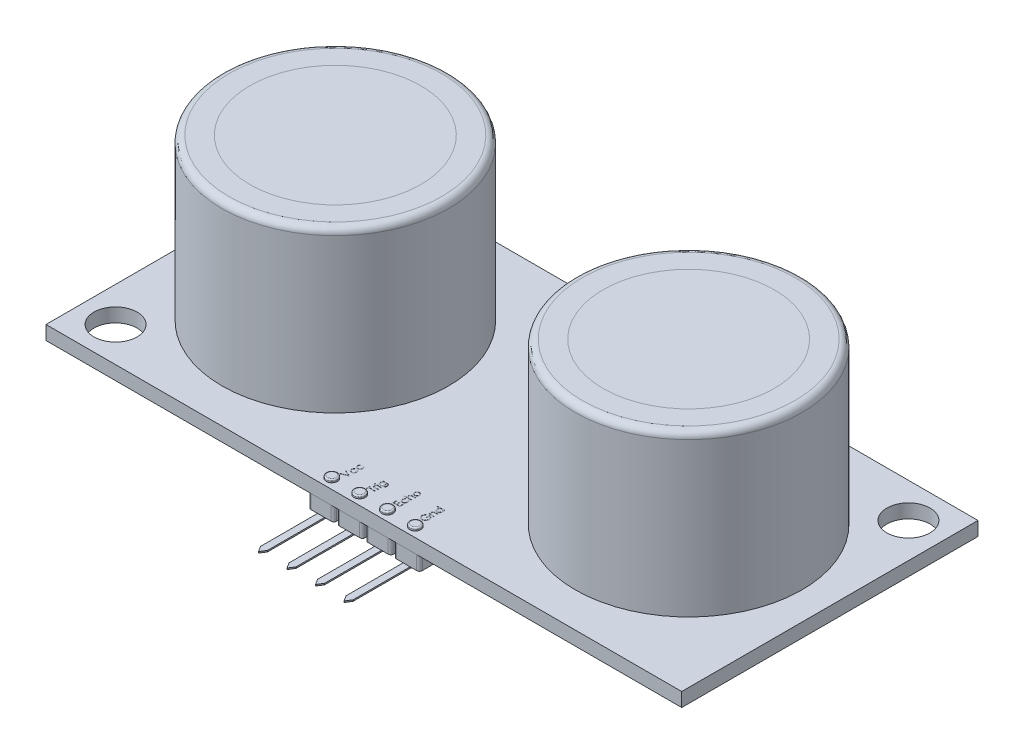
SolidWorks part; units mm, degrees
ref_plane "Front Plane" through (0, 0, 0) normal (0, 0, 1) x (1, 0, 0)
ref_plane "Top Plane" through (0, 0, 0) normal (0, 1, 0) x (1, 0, 0)
ref_plane "Right Plane" through (0, 0, 0) normal (1, 0, 0) x (0, 0, -1)
sketch "Sketch1" plane through (0, 0, 0) normal (0, 1, 0) x (1, 0, 0)
  line L1 (22.85, -10.65) -> (-22.85, -10.65)
  line L2 (22.85, -10.65) -> (22.85, 10.65)
  line L3 (22.85, 10.65) -> (-22.85, 10.65)
  line L4 (-22.85, -10.65) -> (-22.85, 10.65)
  line L5 (22.85, -10.65) -> (-22.85, 10.65) construction
  line L6 (22.85, 10.65) -> (-22.85, -10.65) construction
  circle A0 centre (20.35, 8.15) radius 1.55
  circle A1 centre (-20.35, -8.15) radius 1.55
  point P0 (0, 0)
  dimension "D3" = 3.1
  dimension "D1" = 45.7
  dimension "D2" = 21.3
  dimension "D4" = 2.5
  dimension "D5" = 2.5
  dimension "D6" = 2.5
  dimension "D7" = 2.5
extrude "Boss-Extrude1" add sketch "Sketch1" along normal blind 1
sketch "Sketch2" plane through (0, 1, 0) normal (0, 1, 0) x (1, 0, 0)
  line L0 (0, 0) -> (0, -50000) construction
  circle A0 centre (-12.7, 0) radius 8.15
  circle A1 centre (12.7, 0) radius 8.15
  circle A2 centre (-12.7, 0) radius 6.15
  circle A3 centre (12.7, 0) radius 6.15
  point P4 (20.85, 0)
  point P6 (-20.85, 0)
  dimension "D1" = 16.3
  dimension "D2" = 41.7
  dimension "D3" = 20.85
  dimension "D4" = 2
extrude "Boss-Extrude2" add sketch "Sketch2" along normal blind 11.54 separate body
fillet "Fillet1" radius 0.5 1 edges at (-12.7, 12.54, 8.15)
fillet "Fillet2" radius 0.5 1 edges at (12.7, 12.54, 8.15)
sketch "Sketch3" plane through (0, 1, 0) normal (0, 1, 0) x (1, 0, 0)
  circle A0 centre (-12.7, 0) radius 6
  circle A1 centre (12.7, 0) radius 6
  dimension "D1" = 12
extrude "Boss-Extrude3" add sketch "Sketch3" along normal blind 7 separate body
ref_plane "Plane1" through (12.7, 0, 0) normal (1, 0, 0) x (0, 0, -1)
sketch "Sketch5" plane through (12.7, 0, 0) normal (1, 0, 0) x (0, 0, -1)
  line L0 (0, 8) -> (0, -49992) construction
  line L1 (6, 8) -> (-6, 8) construction
  line L2 (0.75, 8.5) -> (0.75, 8.4)
  line L4 (0.75, 8.5) -> (0, 8.5)
  line L5 (4, 8.915) -> (2, 8)
  line L6 (0.75, 8.4) -> (0.95, 8.4)
  line L7 (0, 8.5) -> (0, 8)
  line L8 (0, 8) -> (2, 8)
  line L9 (0.95, 8.4) -> (4, 8.915)
  point P4 (0, 8)
  dimension "D1" = 4
  dimension "D2" = 0.5
  dimension "D3" = 0.75
  dimension "D4" = 0.1
  dimension "D5" = 2
  dimension "D6" = 15
  dimension "D7" = 0.2
revolve "Revolve1" add sketch "Sketch5" angle 360 about L0
pattern_linear "LPattern2" count 2 spacing 25.4 along (-1, 0, 0) of "Revolve1"
sketch "Sketch6" plane through (0, 12.54, 0) normal (0, 1, 0) x (1, 0, 0)
  circle A0 centre (-12.7, 0) radius 6.15
  circle A1 centre (12.7, 0) radius 6.15
  dimension "D1" = 12.3
extrude "Boss-Extrude4" add sketch "Sketch6" against normal blind 0.2 separate body
sketch "Sketch18" plane through (0, 0, 0) normal (0, -1, 0) x (1, 0, 0)
  line L0 (-22.85, 10.65) -> (22.85, 10.65) construction
  line L1 (-3.8, 10.65) -> (-2.35, 10.65)
  line L2 (-4, 10.45) -> (-4, 8.85)
  line L3 (-3.8, 8.65) -> (-2.35, 8.65)
  line L4 (4, 10.45) -> (4, 8.85)
  line L5 (0, 8.65) -> (0, 10.65) construction
  line L6 (-4, 9.65) -> (4, 9.65) construction
  line L7 (0, 0) -> (0, 50000) construction
  line L8 (-2.15, 10.45) -> (-2.15, 8.85)
  line L9 (0.1, 10.45) -> (0.1, 8.85)
  line L10 (-1.95, 10.45) -> (-1.95, 8.85)
  line L11 (-1.75, 10.65) -> (-0.3, 10.65)
  line L12 (-1.75, 8.65) -> (-0.3, 8.65)
  line L13 (-0.1, 8.85) -> (-0.1, 10.45)
  line L14 (0.3, 10.65) -> (1.75, 10.65)
  line L15 (0.3, 8.65) -> (1.75, 8.65)
  line L16 (1.95, 10.45) -> (1.95, 8.85)
  line L17 (2.15, 10.45) -> (2.15, 8.85)
  line L18 (2.35, 10.65) -> (3.8, 10.65)
  line L19 (2.35, 8.65) -> (3.8, 8.65)
  arc A0 (3.8, 8.65) -> (4, 8.85) centre (3.8, 8.85) ccw
  arc A1 (4, 10.45) -> (3.8, 10.65) centre (3.8, 10.45) ccw
  arc A2 (2.15, 8.85) -> (2.35, 8.65) centre (2.35, 8.85) ccw
  arc A3 (2.15, 10.45) -> (2.35, 10.65) centre (2.35, 10.45) cw
  arc A4 (1.95, 8.85) -> (1.75, 8.65) centre (1.75, 8.85) cw
  arc A5 (1.95, 10.45) -> (1.75, 10.65) centre (1.75, 10.45) ccw
  arc A6 (0.1, 8.85) -> (0.3, 8.65) centre (0.3, 8.85) ccw
  arc A7 (0.1, 10.45) -> (0.3, 10.65) centre (0.3, 10.45) cw
  arc A8 (-0.1, 8.85) -> (-0.3, 8.65) centre (-0.3, 8.85) cw
  arc A9 (-0.1, 10.45) -> (-0.3, 10.65) centre (-0.3, 10.45) ccw
  arc A10 (-1.95, 10.45) -> (-1.75, 10.65) centre (-1.75, 10.45) cw
  arc A11 (-1.95, 8.85) -> (-1.75, 8.65) centre (-1.75, 8.85) ccw
  arc A12 (-2.35, 8.65) -> (-2.15, 8.85) centre (-2.35, 8.85) ccw
  arc A13 (-2.15, 10.45) -> (-2.35, 10.65) centre (-2.35, 10.45) ccw
  arc A14 (-4, 8.85) -> (-3.8, 8.65) centre (-3.8, 8.85) ccw
  arc A15 (-4, 10.45) -> (-3.8, 10.65) centre (-3.8, 10.45) cw
  point P24 (4, 10.65)
  point P27 (2.15, 8.65)
  point P30 (2.15, 10.65)
  point P33 (1.95, 8.65)
  point P38 (0.1, 8.65)
  point P41 (0.1, 10.65)
  point P46 (-0.1, 10.65)
  point P49 (-1.95, 10.65)
  point P52 (-1.95, 8.65)
  point P59 (-4, 8.65)
  point P62 (-4, 10.65)
  point P212 (0, 9.65)
  dimension "D1" = 8
  dimension "D10" = 0.2
  dimension "D2" = 2
  dimension "D3" = 1.85
  dimension "D4" = 0.2
  dimension "D5" = 1.85
  dimension "D6" = 0.2
  dimension "D7" = 0.2
  dimension "D8" = 1.85
  dimension "D9" = 4
extrude "Boss-Extrude10" add sketch "Sketch18" along normal blind 1 separate body
sketch "Sketch13" plane through (0, 1, 0) normal (0, 1, 0) x (1, 0, 0)
  line L0 (-4, -10.65) -> (-4, -8.7338) construction
  line L1 (-22.85, -10.65) -> (22.85, -10.65) construction
  line L2 (-4, -8.7338) -> (4, -8.7338) construction
  line L3 (4, -8.7338) -> (4, -10.65) construction
  line L4 (4, -10.65) -> (-4, -10.65) construction
  line L5 (0, 0) -> (0, -50000) construction
  circle A0 centre (-3, -9.95) radius 0.4
  circle A1 centre (-1, -9.95) radius 0.4
  circle A2 centre (1, -9.95) radius 0.4
  circle A3 centre (3, -9.95) radius 0.4
  point P9 (-4, -9.6919)
  dimension "D8" = 0.8
  dimension "D1" = 8
  dimension "D2" = 4
  dimension "D3" = 0.7
  dimension "D4" = 2
  dimension "D5" = 2
  dimension "D6" = 2
  dimension "D7" = 1
extrude "Boss-Extrude8" add sketch "Sketch13" along normal blind 0.2 separate body
fillet "Fillet3" radius 0.1 1 edges at (-3, 1.2, 10.35)
fillet "Fillet4" radius 0.1 1 edges at (-1, 1.2, 10.35)
fillet "Fillet5" radius 0.1 1 edges at (1, 1.2, 10.35)
fillet "Fillet6" radius 0.1 1 edges at (3, 1.2, 10.35)
sketch "Sketch15" plane through (0, 1, 0) normal (0, 1, 0) x (1, 0, 0)
  line L0 (-22.85, -10.65) -> (22.85, -10.65) construction
  line L1 (3.4865, -7.65) -> (-2.4849, -7.65) construction
  line L2 (3.4865, -7.65) -> (3.4865, -10.65) construction
  line L3 (3.4865, -10.65) -> (-2.4849, -10.65) construction
  line L5 (-2.4849, -7.65) -> (-2.4849, -10.65) construction
  line L6 (3.4865, -7.65) -> (-2.4849, -10.65) construction
  line L7 (3.4865, -10.65) -> (-2.4849, -7.65) construction
  text T0 "Vcc  \r\nTrig   \r\nEcho\r\nGnd " font "Century Gothic" height 0.5
  point P0 (0.5008, -9.15)
  dimension "D1" = 3
extrude "Cut-Extrude5" cut sketch "Sketch15" against normal blind 0.01
sketch "Sketch19" plane through (0, -1, 0) normal (0, -1, 0) x (1, 0, 0)
  line L1 (3.325, 9.15) -> (2.825, 9.15)
  line L2 (3.325, 9.15) -> (3.325, 14.75)
  line L3 (3.075, 15.15) -> (2.825, 15.15)
  line L4 (2.825, 9.15) -> (2.825, 14.75)
  line L5 (3.075, 15.15) -> (3.075, 9.15) construction
  line L6 (3.325, 12.15) -> (2.825, 12.15) construction
  line L7 (1.275, 9.15) -> (0.775, 9.15)
  line L8 (1.275, 9.15) -> (1.275, 14.75)
  line L9 (1.025, 15.15) -> (0.775, 15.15)
  line L10 (0.775, 9.15) -> (0.775, 14.75)
  line L11 (1.025, 15.15) -> (1.025, 9.15) construction
  line L12 (1.275, 12.15) -> (0.775, 12.15) construction
  line L13 (-0.775, 9.15) -> (-1.275, 9.15)
  line L14 (-0.775, 9.15) -> (-0.775, 14.75)
  line L15 (-1.025, 15.15) -> (-1.275, 15.15)
  line L16 (-1.275, 9.15) -> (-1.275, 14.75)
  line L17 (-1.025, 15.15) -> (-1.025, 9.15) construction
  line L18 (-0.775, 12.15) -> (-1.275, 12.15) construction
  line L19 (-2.825, 9.15) -> (-3.325, 9.15)
  line L20 (-2.825, 9.15) -> (-2.825, 14.75)
  line L21 (-3.075, 15.15) -> (-3.325, 15.15)
  line L22 (-3.325, 9.15) -> (-3.325, 14.75)
  line L23 (-3.075, 15.15) -> (-3.075, 9.15) construction
  line L24 (-2.825, 12.15) -> (-3.325, 12.15) construction
  line L26 (-1.75, 8.65) -> (-0.3, 8.65) construction
  line L27 (-3.8, 8.65) -> (-2.35, 8.65) construction
  line L29 (-3.075, 15.15) -> (-2.825, 14.75)
  line L30 (-3.075, 15.15) -> (-3.325, 14.75)
  line L31 (-1.025, 15.15) -> (-0.775, 14.75)
  line L32 (1.025, 15.15) -> (1.275, 14.75)
  line L33 (-1.275, 14.75) -> (-1.025, 15.15)
  line L34 (1.025, 15.15) -> (0.775, 14.75)
  line L35 (3.075, 15.15) -> (3.325, 14.75)
  line L37 (2.825, 14.75) -> (3.075, 15.15)
  point P20 (-1.025, 8.65)
  point P23 (-3.075, 8.65)
  point P300 (-1.025, 12.15)
  point P301 (-3.075, 12.15)
  point P352 (1.025, 12.15)
  point P420 (3.075, 12.15)
  dimension "D2" = 6
  dimension "D3" = 0.5
  dimension "D4" = 0.5
  dimension "D5" = 0.5
  dimension "D6" = 0.5
  dimension "D7" = 0.4
  dimension "D8" = 0.4
  dimension "D9" = 0.4717
extrude "Boss-Extrude11" add sketch "Sketch19" along normal blind 0.1 separate body contours L29 L20 L19 L22 L30 | L31 L14 L13 L16 L33 | L32 L8 L7 L10 L34 | L35 L2 L1 L4 L37
sketch "Sketch21" plane through (0, 1, 0) normal (0, 1, 0) x (1, 0, 0)
  line L0 (22.85, 10.65) -> (-22.85, 10.65) construction
  line L1 (3, 6.65) -> (-3, 6.65)
  line L3 (3, 9.65) -> (-3, 9.65)
  arc A0 (-3, 9.65) -> (-3, 6.65) centre (-3, 8.15) ccw
  arc A1 (3, 6.65) -> (3, 9.65) centre (3, 8.15) ccw
  point P14 (-4.5, 8.15)
  point P16 (4.5, 8.15)
  dimension "D1" = 3
  dimension "D2" = 6
  dimension "D3" = 1
extrude "Boss-Extrude13" add sketch "Sketch21" along normal blind 0.5 separate body
sketch "Sketch22" plane through (0, 1.5, 0) normal (0, 1, 0) x (1, 0, 0)
  line L1 (-2.9874, 7.15) -> (3, 7.15)
  line L3 (-3, 9.15) -> (3, 9.15)
  line L4 (-3, 6.65) -> (3, 6.65) construction
  arc A0 (-3, 9.15) -> (-2.9874, 7.15) centre (-3, 8.15) ccw
  arc A1 (3, 7.15) -> (3, 9.15) centre (3, 8.15) ccw
  arc A2 (-3, 9.65) -> (-3, 6.65) centre (-3, 8.15) ccw construction
  arc A3 (3, 6.65) -> (3, 9.65) centre (3, 8.15) ccw construction
  point P2 (4.5, 8.15)
  point P3 (4, 8.15)
  point P4 (-4.5, 8.15)
  point P5 (-4, 8.1437)
  dimension "D1" = 0.5
  dimension "D3" = 1
  dimension "D2" = 2
  dimension "D4" = 0.5
  dimension "D5" = 0.5
extrude "Boss-Extrude14" add sketch "Sketch22" along normal blind 1.5
fillet "Fillet7" radius 0.1 8 edges at (-4, 3, -8.1437) (0, 3, -9.15) (4, 3, -8.15) (-4.5, 1.5, -8.15) (0, 1.5, -9.65) (4.5, 1.5, -8.15) (0.0063, 3, -7.15) (0, 1.5, -6.65)
ref_plane "Plane2" through (22.85, 0, -10.65) normal (-1, 0, 0) x (0, 0, 1)
sketch "Sketch24" plane through (0, 0, -10.65) normal (0, 0, -1) x (-1, 0, 0)
  line L0 (0, 1) -> (-65.2631, 496.7224)
  line L1 (-22.85, 1) -> (22.85, 1) construction
  line L2 (-65.2631, 496.7224) -> (65.2631, 496.7224)
  line L3 (65.2631, 496.7224) -> (0, 1)
  line L6 (-3, 2.9) -> (-3, 1.5) construction
  dimension "D1" = 15
  dimension "D2" = 82.5
  dimension "D3" = 500
  dimension "D4" = 3
equation "\"D2@Sketch13\"=\"D1@Sketch13\"/2"
equation "\"D9@Sketch18\"=\"D1@Sketch18\"/2"
